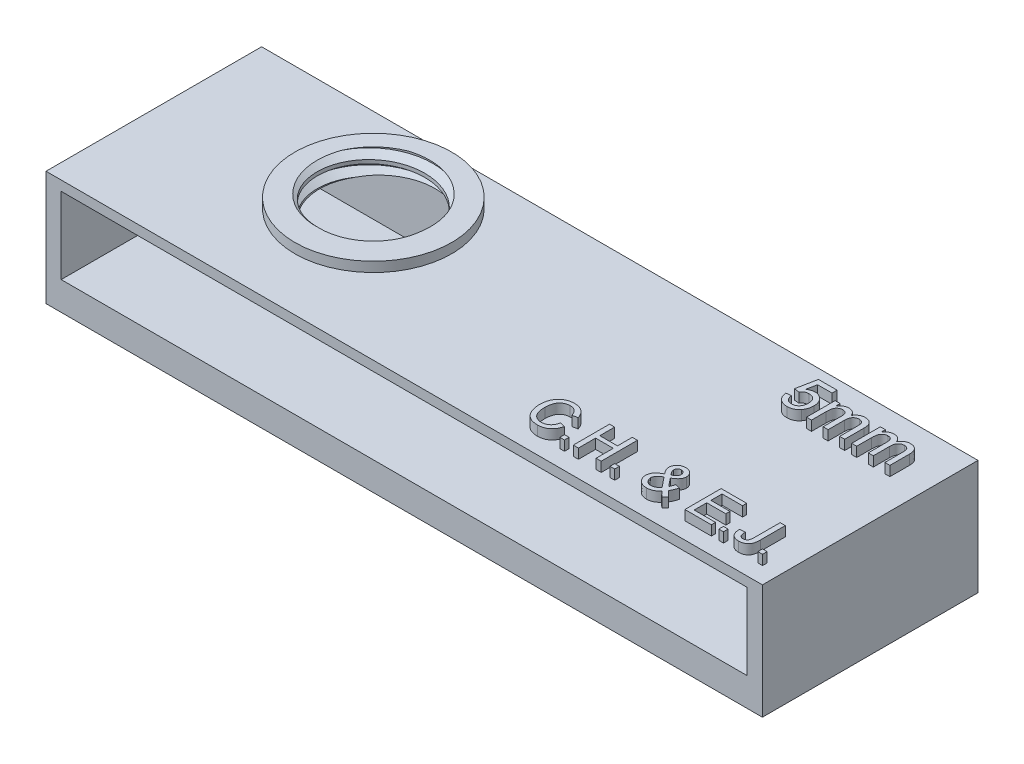
SolidWorks part; units mm, degrees
ref_plane "Ebene vorne" through (0, 0, 0) normal (0, 0, 1) x (1, 0, 0)
ref_plane "Ebene oben" through (0, 0, 0) normal (0, 1, 0) x (1, 0, 0)
ref_plane "Ebene rechts" through (0, 0, 0) normal (1, 0, 0) x (0, 0, -1)
sketch "Skizze1" plane through (0, 0, 0) normal (0, 1, 0) x (1, 0, 0)
  line L1 (-46.4165, 18.2033) -> (26.6835, 18.2033)
  line L2 (-46.4165, 18.2033) -> (-46.4165, -3.7967)
  line L3 (-46.4165, -3.7967) -> (26.6835, -3.7967)
  line L4 (26.6835, 18.2033) -> (26.6835, -3.7967)
  dimension "D1" = 73.1
  dimension "D2" = 22
extrude "Basis" add sketch "Skizze1" along normal blind 11.7
ref_plane "Ebene seitlich Handyschlitz" through (0, 0, 3.7967) normal (0, 0, 1) x (1, 0, 0)
sketch "Skizze2" plane through (0, 0, 3.7967) normal (0, 0, 1) x (1, 0, 0)
  line L1 (-44.8665, 10.7) -> (25.1335, 10.7)
  line L2 (-44.8665, 10.7) -> (-44.8665, 2.9)
  line L3 (-44.8665, 2.9) -> (25.1335, 2.9)
  line L4 (25.1335, 10.7) -> (25.1335, 2.9)
  line L5 (-46.4165, 11.7) -> (-46.4165, 0) construction
  line L6 (-46.4165, 11.7) -> (26.6835, 11.7) construction
  point P8 (0, 0)
  dimension "D1" = 70
  dimension "D2" = 7.8
  dimension "D3" = 1
  dimension "D4" = 1.55
extrude "Handyschlitz" cut sketch "Skizze2" against normal blind 21.25
ref_plane "Ebene oben auf Basis für Zylinder" through (0, 11.7, 0) normal (0, 1, 0) x (1, 0, 0)
sketch "Skizze3" plane through (0, 11.7, 0) normal (0, 1, 0) x (1, 0, 0)
  line L0 (-46.4165, 18.2033) -> (-46.4165, -3.7967) construction
  line L1 (26.6835, 18.2033) -> (-46.4165, 18.2033) construction
  circle A0 centre (-26.4165, 9.6033) radius 6.3
  dimension "D1" = 20
  dimension "D2" = 8.6
extrude "Zylinder" add sketch "Skizze3" along normal blind 1
ref_plane "Ebene oben auf Zylinder" through (0, 12.7, 0) normal (0, 1, 0) x (1, 0, 0)
sketch "Skizze6" plane through (0, 11.7, 0) normal (0, 1, 0) x (1, 0, 0)
  circle A0 centre (-26.4165, 9.6033) radius 8
extrude "Aufsatz-Linear austragen1" add sketch "Skizze6" along normal blind 1 contours A0
sketch "Skizze8" plane through (0, 12.7, 0) normal (0, 1, 0) x (1, 0, 0)
  circle A0 centre (-26.4165, 9.6033) radius 6.3
extrude "Schnitt-Linear austragen2" cut sketch "Skizze8" against normal blind 6
ref_plane "Ebene3" through (0, 10.7, 0) normal (0, -1, 0) x (-1, 0, 0)
sketch "Skizze12" plane through (0, 12.7, 0) normal (0, 1, 0) x (1, 0, 0)
  circle A0 centre (-26.4165, 9.6033) radius 7.5
thread "Gewinde2" pitch 1.5 method extrude profile "Gewindeprofil2" start angle 0, offset 1.6, length 8, pitch 1.5, diameter 12.6
ref_plane "Ebene5" through (-32.7165, 14.3, -9.6033) normal (0, 0, 1) x (-1, 0, 0)
sketch "Gewindeprofil2" plane through (-32.7165, 14.3, -9.6033) normal (0, 0, 1) x (-1, 0, 0)
  line L0 (0, 0) -> (0, 1.5) construction
  line L11 (0, 0) -> (0, 1.3125)
  line L12 (0, 1.3125) -> (-0.8119, 0.8437)
  line L13 (-0.8119, 0.8437) -> (-0.8119, 0.4687)
  line L15 (-0.8119, 0.4687) -> (0, 0)
  line L17 (-0.8119, 0.6562) -> (0, 0.6562) construction
  point P2 (0, 0)
  dimension "Pitch" = 1.5
  dimension "Profile_Angle" = 60
  dimension "Profile_Land" = 0.375
  dimension "Profile_Height" = 0.8119
extrude "Schnitt-Linear austragen5" cut sketch "Skizze12" along normal blind 6 contours A0
sketch "Skizze17" plane through (0, 10.7, 0) normal (0, -1, 0) x (-1, 0, 0)
  line L1 (13.3814, 0) -> (43.6823, 0)
  line L2 (13.3814, 0) -> (13.3814, 16.2694)
  line L3 (13.3814, 16.2694) -> (43.6823, 16.2694)
  line L4 (43.6823, 0) -> (43.6823, 16.2694)
extrude "Schnitt-Linear austragen7" cut sketch "Skizze17" along normal blind 6
ref_plane "Ebene für Logo" through (0, 0, 0) normal (0, -1, 0) x (-1, 0, 0)
sketch "Skizze24" plane through (0, 0, 0) normal (0, -1, 0) x (-1, 0, 0)
  line L1 (33.7615, 1.4341) -> (32.0294, -1.5659)
  line L2 (32.0294, -1.5659) -> (35.4935, -1.5659)
  line L3 (35.4935, -1.5659) -> (33.7615, 1.4341)
  line L4 (35.9478, -1.5381) -> (37.6798, 1.4619)
  line L5 (37.6798, 1.4619) -> (34.2157, 1.4619)
  line L6 (34.2157, 1.4619) -> (35.9478, -1.5381)
  line L7 (38.0931, 1.4341) -> (36.3611, -1.5659)
  line L8 (36.3611, -1.5659) -> (39.8252, -1.5659)
  line L9 (39.8252, -1.5659) -> (38.0931, 1.4341)
  line L10 (40.2382, -1.5381) -> (41.9702, 1.4619)
  line L11 (41.9702, 1.4619) -> (38.5061, 1.4619)
  line L12 (38.5061, 1.4619) -> (40.2382, -1.5381)
  line L13 (42.3422, 1.4341) -> (40.6101, -1.5659)
  line L14 (40.6101, -1.5659) -> (44.0742, -1.5659)
  line L15 (44.0742, -1.5659) -> (42.3422, 1.4341)
  line L16 (35.9475, 4.8546) -> (34.2154, 1.8546)
  line L17 (34.2154, 1.8546) -> (37.6795, 1.8546)
  line L18 (37.6795, 1.8546) -> (35.9475, 4.8546)
  line L19 (38.1338, 1.9341) -> (39.8658, 4.9341)
  line L20 (39.8658, 4.9341) -> (36.4017, 4.9341)
  line L21 (36.4017, 4.9341) -> (38.1338, 1.9341)
  line L22 (40.2791, 4.8546) -> (38.547, 1.8546)
  line L23 (38.547, 1.8546) -> (42.0111, 1.8546)
  line L24 (42.0111, 1.8546) -> (40.2791, 4.8546)
  line L28 (38.1338, 8.3316) -> (36.4017, 5.3316)
  line L29 (36.4017, 5.3316) -> (39.8658, 5.3316)
  line L30 (39.8658, 5.3316) -> (38.1338, 8.3316)
  circle A0 centre (33.7615, -0.5659) radius 1 construction
  circle A1 centre (35.9478, 0.4619) radius 1 construction
  circle A2 centre (38.0931, -0.5659) radius 1 construction
  circle A3 centre (40.2382, 0.4619) radius 1 construction
  circle A4 centre (42.3422, -0.5659) radius 1 construction
  circle A5 centre (35.9475, 2.8546) radius 1 construction
  circle A6 centre (38.1338, 3.9341) radius 1 construction
  circle A7 centre (40.2791, 2.8546) radius 1 construction
  circle A8 centre (38.1338, 6.3316) radius 1 construction
sketch "Skizze25" plane through (0, 0, 0) normal (0, -1, 0) x (-1, 0, 0)
  text T0 "EAH JENA         " font "Arial" height 3.5
extrude "EAH Jena" add sketch "Skizze25" along normal blind 1
extrude "LOGO" add sketch "Skizze24" along normal blind 1
ref_plane "Ebene für Schrift oben" through (0, 11.7, 0) normal (0, 1, 0) x (1, 0, 0)
sketch "Skizze26" plane through (0, 11.7, 0) normal (0, 1, 0) x (1, 0, 0)
  text T0 "C.H. & E.J." font "Arial" height 3.7
extrude "C.H. & E.J." add sketch "Skizze26" along normal blind 1
sketch "Skizze27" plane through (0, 11.7, 0) normal (0, 1, 0) x (1, 0, 0)
  text T0 "5mm" font "Arial" height 4
extrude "5mm" add sketch "Skizze27" along normal blind 1
